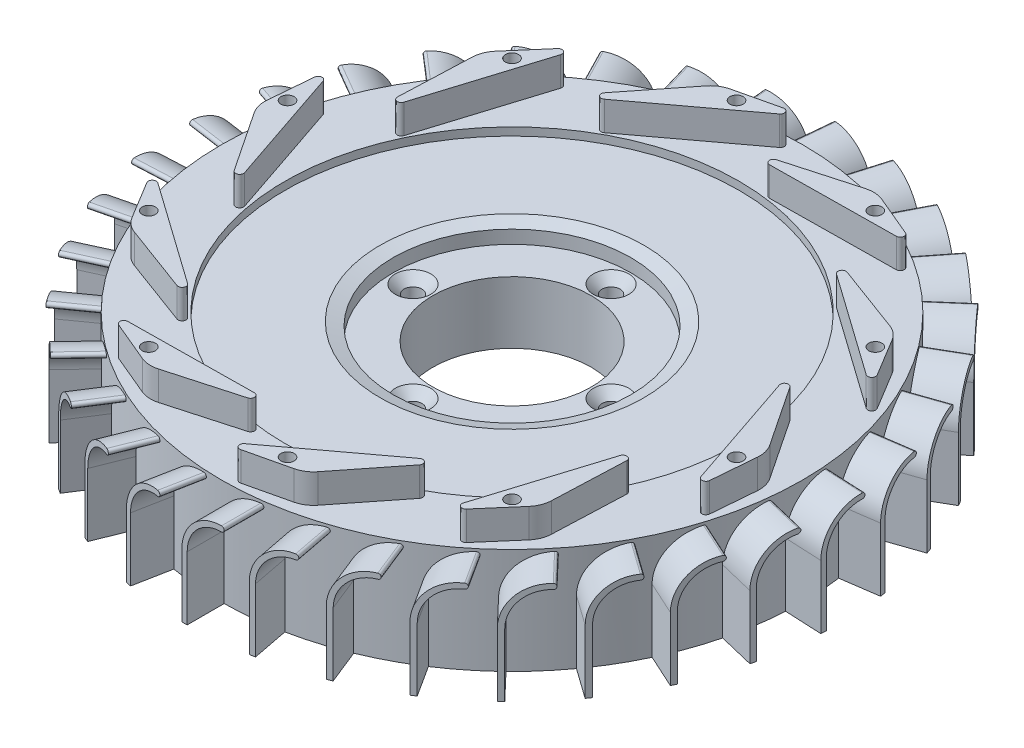
SolidWorks part; units mm, degrees
ref_plane "Ön Düzlem" through (0, 0, 0) normal (0, 0, 1) x (1, 0, 0)
ref_plane "Üst Düzlem" through (0, 0, 0) normal (0, 1, 0) x (1, 0, 0)
ref_plane "Sağ Düzlem" through (0, 0, 0) normal (1, 0, 0) x (0, 0, -1)
sketch "Çizim1" plane through (0, 0, 0) normal (0, 0, 1) x (1, 0, 0)
  line L0 (0, -11.0242) -> (0, 16.3693) construction
  line L1 (-55, 25.4927) -> (-43, 25.4927)
  line L2 (-43, 25.4927) -> (-43, 23.9927)
  line L3 (-43, 23.9927) -> (-25, 23.9927)
  line L4 (-25, 23.9927) -> (-22.5, 23.2284)
  line L5 (-22.5, 23.2284) -> (-22.5, 20.7427)
  line L6 (-22.5, 20.7427) -> (-15, 20.7427)
  line L7 (-15, 20.7427) -> (-15, 8.9927)
  line L8 (-15, 8.9927) -> (-22.5, 8.9927)
  line L9 (-22.5, 8.9927) -> (-22.5, 3.9927)
  line L10 (-22.5, 3.9927) -> (-24.5, 3.9927)
  line L11 (-24.5, 3.9927) -> (-29.83, 15.4927)
  line L12 (-29.83, 15.4927) -> (-47, 15.4927)
  line L13 (-52, 10.4927) -> (-52, 5.4927)
  line L14 (-52, 5.4927) -> (-55, 5.4927)
  line L15 (-55, 5.4927) -> (-55, 25.4927)
  arc A0 (-47, 15.4927) -> (-52, 10.4927) centre (-47, 10.4927) ccw
  point P25 (-52, 15.4927)
  dimension "D17" = 5
  dimension "D1" = 55
  dimension "D2" = 15
  dimension "D3" = 7.5
  dimension "D4" = 2
  dimension "D5" = 22.5
  dimension "D6" = 25
  dimension "D7" = 43
  dimension "D8" = 107
  dimension "D9" = 3
  dimension "D10" = 17.17
  dimension "D11" = 10
  dimension "D12" = 1.5
  dimension "D13" = 20
  dimension "D14" = 5
  dimension "D15" = 11.75
  dimension "D16" = 16.5
  dimension "D18" = 18
revolve "Döndür1" add sketch "Çizim1" angle 360 about L0 other way angle 360
ref_plane "Düzlem1" through (0, 0, 53) normal (0, 0, 1) x (1, 0, 0)
sketch "Çizim2" plane through (0, 0, 53) normal (0, 0, 1) x (1, 0, 0)
  line L0 (0, -4.349) -> (0, 36.2842) construction
  line L3 (0.5, 5.4927) -> (0.5, 17.4927)
  line L4 (-0.5, 5.4927) -> (-0.5, 17.4927)
  line L6 (7, 17.4927) -> (7, 28.8863) construction
  line L7 (-0.5, 5.4927) -> (0.5, 5.4927)
  arc A1 (7, 24.9927) -> (-0.5, 17.4927) centre (7, 17.4927) ccw
  arc A2 (7, 23.9927) -> (0.5, 17.4927) centre (7, 17.4927) ccw
  arc A6 (7, 23.9927) -> (7, 24.9927) centre (7, 24.4927) ccw
extrude "Yükseklik-Ekstrüzyon1" add sketch "Çizim2" along normal blind 9
pattern_circular "Dairesel Kaplama1" count 33 over 360 about axis through (0, 5.4927, 0) along (0, -1, 0) of "Yükseklik-Ekstrüzyon1"
sketch "Çizim9" plane through (0, 25.4927, 0) normal (0, 1, 0) x (1, 0, 0)
  line L0 (0, 0) -> (0, 43) construction
  line L1 (5.4846, 44.5404) -> (18.6661, 48.2426)
  line L2 (21.9558, 48.0381) -> (29.6721, 44.7942)
  line L3 (29.3905, 43.3529) -> (5.6964, 43.0684)
  arc A2 (29.6721, 44.7942) -> (29.3905, 43.3529) centre (29.3814, 44.1028) cw
  arc A3 (5.4846, 44.5404) -> (5.6964, 43.0684) centre (5.6874, 43.8183) ccw
  arc A4 (18.6661, 48.2426) -> (21.9558, 48.0381) centre (20.0181, 43.4288) cw
  point P31 (32.9976, 43.3962)
  dimension "D4" = 0.75
  dimension "D5" = 5
  dimension "D1" = 43
  dimension "D2" = 33
  dimension "D3" = 15
extrude "Yükseklik-Ekstrüzyon2" add sketch "Çizim9" along normal blind 5.5
pattern_circular "Dairesel Kaplama3" count 10 over 360 about axis through (0, 25.4927, 0) along (0, -1, 0) of "Yükseklik-Ekstrüzyon2"
sketch "Çizim11" plane through (0, 25.4927, 0) normal (0, 1, 0) x (1, 0, 0)
  line L0 (0, -5.5747) -> (0, 94.5529) construction
  point P3 (-8, 50.5)
  dimension "D1" = 50.5
  dimension "D2" = 8
hole_wizard "M3 Dişli Delik2" positions "Çizim13" profile "Çizim14" tap size "M3" standard "ISO" end condition through all
sketch "Çizim13" plane through (0, 30.9927, 0) normal (0, 1, 0) x (1, 0, 0)
  point P0 (-8, 50.5)
sketch "Çizim14" plane through (-8, 30.9927, -50.5) normal (1, 0, 0) x (0, 0, 1)
  line L0 (0, 0) -> (0, 27)
  line L1 (0, 27) -> (1.25, 27)
  line L2 (1.25, 27) -> (1.25, 0)
  line L5 (1.25, 0) -> (0, 0)
  line L11 (0, -6.35) -> (0, 107.95) construction
  dimension "Thru Tap Drill Dia." = 2.5
  dimension "Thru Tap Drill Depth" = 27
cosmetic thread "Delik Dişi2" parameters "D2"=3
pattern_circular "Dairesel Kaplama4" count 10 over 360 about axis through (0, 25.4927, 0) along (0, -1, 0) of "M3 Dişli Delik2"
cosmetic thread "Delik Dişi3" parameters "D2"=3
cosmetic thread "Delik Dişi4" parameters "D2"=3
cosmetic thread "Delik Dişi5" parameters "D2"=3
cosmetic thread "Delik Dişi6" parameters "D2"=3
cosmetic thread "Delik Dişi7" parameters "D2"=3
cosmetic thread "Delik Dişi8" parameters "D2"=3
cosmetic thread "Delik Dişi9" parameters "D2"=3
cosmetic thread "Delik Dişi10" parameters "D2"=3
cosmetic thread "Delik Dişi11" parameters "D2"=3
sketch "Çizim15" plane through (0, 20.7427, 0) normal (0, 1, 0) x (1, 0, 0)
  line L0 (0, 0) -> (0, 18.75) construction
  point P4 (0, 18.75)
  dimension "D1" = 18.75
hole_wizard "M3 Altıgen Alyan Havşa Başlı Kör Vida İçin Havşa1" positions "3B Çizim1" profile "Çizim16" countersink size "M3" standard "ISO" end condition through all
sketch3d "3B Çizim1"
  point P0 (0, 20.7427, -18.75)
sketch "Çizim16" plane through (0, 20.7427, -18.75) normal (1, 0, 0) x (0, 0, 1)
  line L0 (0, 0) -> (0, 16.75)
  line L1 (0, 16.75) -> (1.7, 16.75)
  line L2 (1.7, 16.75) -> (1.7, 1.66)
  line L3 (1.7, 1.66) -> (3.36, 0)
  line L5 (3.36, 0) -> (0, 0)
  line L6 (-1.7, 1.66) -> (-3.36, 0) construction
  line L11 (0, -6.35) -> (0, 107.95) construction
  dimension "Thru Hole Dia." = 3.4
  dimension "Thru Hole Depth" = 16.75
  dimension "Near C'Sink Dia." = 6.72
  dimension "Near C'Sink Angle" = 90
pattern_circular "Dairesel Kaplama5" count 4 over 360 about axis through (0, 20.7427, 0) along (0, -1, 0) of "M3 Altıgen Alyan Havşa Başlı Kör Vida İçin Havşa1"
